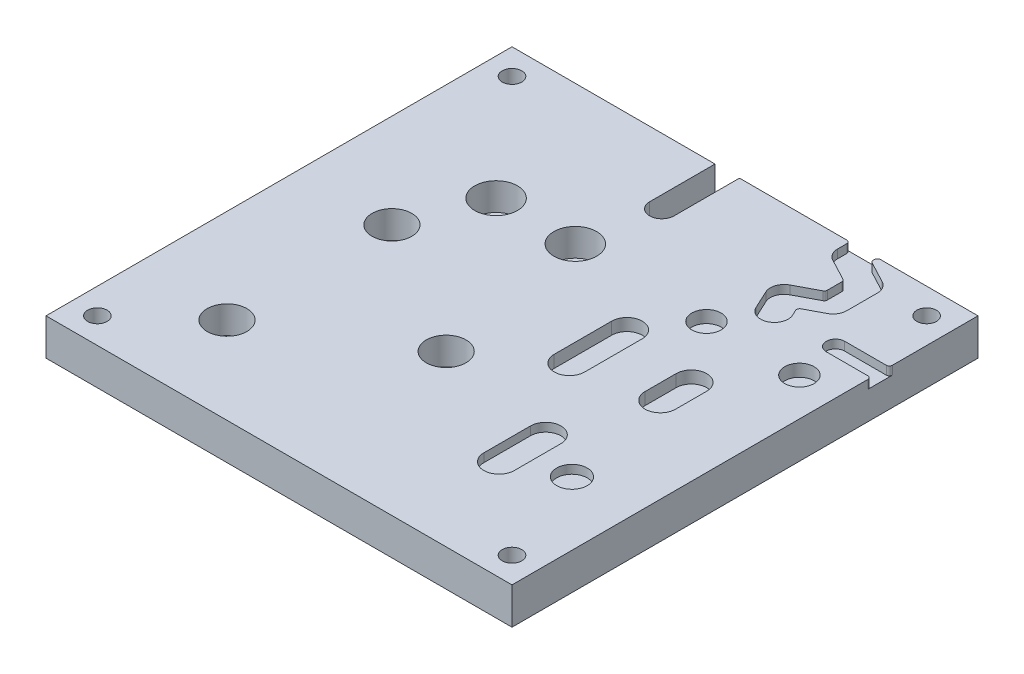
SolidWorks part; units mm, degrees
ref_plane "Front Plane" through (0, 0, 0) normal (0, 0, 1) x (1, 0, 0)
ref_plane "Top Plane" through (0, 0, 0) normal (0, 1, 0) x (1, 0, 0)
ref_plane "Right Plane" through (0, 0, 0) normal (1, 0, 0) x (0, 0, -1)
sketch "Base plate" plane through (0, 0, 0) normal (0, 1, 0) x (1, 0, 0)
  line L0 (-2.9, 38.1) -> (-2.9, 27.4) construction
  line L1 (-33.9, -38.1) -> (33.9, -38.1)
  line L2 (-38.1, -33.9) -> (-38.1, 33.9)
  line L3 (-33.9, 38.1) -> (33.9, 38.1)
  line L4 (38.1, -33.9) -> (38.1, 33.9)
  line L5 (-38.1, -38.1) -> (38.1, 38.1) construction
  line L6 (-38.1, 38.1) -> (38.1, -38.1) construction
  line L7 (-0.9, 38.1) -> (-0.9, 27.4)
  line L8 (-4.9, 38.1) -> (-4.9, 27.4)
  line L9 (-33.9, 38.1) -> (-38.1, 38.1)
  line L10 (-38.1, 38.1) -> (-38.1, 33.9)
  line L11 (-38.1, -33.9) -> (-38.1, -38.1)
  line L12 (-38.1, -38.1) -> (-33.9, -38.1)
  line L13 (33.9, -38.1) -> (38.1, -38.1)
  line L14 (38.1, -38.1) -> (38.1, -33.9)
  line L15 (38.1, 33.9) -> (38.1, 38.1)
  line L16 (38.1, 38.1) -> (33.9, 38.1)
  circle A0 centre (-33.9, 33.9) radius 1.6
  circle A1 centre (33.9, 33.9) radius 1.6
  circle A2 centre (33.9, -33.9) radius 1.6
  circle A3 centre (-33.9, -33.9) radius 1.6
  arc A4 (-33.9, -38.1) -> (-38.1, -33.9) centre (-33.9, -33.9) cw construction
  arc A5 (33.9, -38.1) -> (38.1, -33.9) centre (33.9, -33.9) ccw construction
  arc A6 (33.9, 38.1) -> (38.1, 33.9) centre (33.9, 33.9) cw construction
  arc A7 (-38.1, 33.9) -> (-33.9, 38.1) centre (-33.9, 33.9) cw construction
  arc A9 (-4.9, 27.4) -> (-0.9, 27.4) centre (-2.9, 27.4) ccw
  point P0 (0, 0)
  dimension "D2" = 3.2
  dimension "D4" = 4.2
  dimension "D5" = 2
  dimension "D6" = 12.7
  dimension "D1" = 76.2
  dimension "D3" = 4.2
  dimension "D7" = 39
extrude "凸台-拉伸1" add sketch "Base plate" along normal blind 6 contours A9 L8 L3 A7 L2 A4 L1 A5 L4 A6 L7 A3 A2 A1 A0 region at (0.0249, 0, 0.274)
fillet "圆角1" [suppressed] radius 1
sketch "草图1" plane through (0, 0, 0) normal (0, -1, 0) x (1, 0, 0)
  line L0 (456, 1824) -> (2280, 1824) construction
  line L1 (-33.9, -33.9) -> (33.9, -33.9) construction
  line L3 (-0.35, 10.415) -> (-22.7, 10.415) construction
  line L6 (11.4, 2) -> (11.4, -7.4) construction
  line L7 (13.9, 2) -> (13.9, -7.4)
  line L8 (8.9, 2) -> (8.9, -7.4)
  line L9 (24.1, -0.16) -> (24.1, -5.24) construction
  line L10 (26.6, -0.16) -> (26.6, -5.24)
  line L11 (21.6, -0.16) -> (21.6, -5.24)
  line L12 (24.1, -2.7) -> (11.4, -2.7) construction
  line L13 (19.6, 21.71) -> (19.6, 14.09) construction
  line L14 (22.1, 21.71) -> (22.1, 14.09)
  line L15 (17.1, 21.71) -> (17.1, 14.09)
  line L16 (30.8, -22.1) -> (38.1, -22.1) construction
  line L17 (30.8, -20.6) -> (38.1, -20.6)
  line L18 (30.8, -23.6) -> (38.1, -23.6)
  line L19 (27.7, 17.9) -> (19.6, 17.9) construction
  line L24 (16.7, -15.1) -> (31.9, -15.1) construction
  line L25 (38.1, -20.6) -> (38.1, -23.6)
  line L26 (24.4, -28.1) -> (24.4, -33.1) construction
  line L27 (26.65, -28.1) -> (26.65, -33.1)
  line L28 (22.15, -28.1) -> (22.15, -33.1)
  line L29 (20.8, -22.1) -> (19.4, -25.1) construction
  line L30 (22.8389, -23.0515) -> (21.4389, -26.0515)
  line L31 (18.7611, -21.1485) -> (17.3611, -24.1485)
  line L32 (19.4, -36.1) -> (19.4, -38.1) construction
  line L33 (-0.9, -38.1) -> (38.1, -38.1) construction
  line L34 (21.65, -36.1) -> (21.65, -38.1)
  line L35 (17.15, -36.1) -> (17.15, -38.1)
  line L36 (17.15, -38.1) -> (21.65, -38.1)
  line L37 (24.4, -30.6) -> (19.4, -30.6) construction
  line L38 (19.4, -25.1) -> (19.4, -36.1) construction
  line L39 (30.8, -22.1) -> (20.8, -22.1) construction
  line L40 (18.348, -34.1111) -> (22.15, -32.1)
  line L41 (25.452, -35.0889) -> (21.65, -37.1)
  line L42 (18.348, -27.0889) -> (22.15, -29.1)
  line L43 (25.452, -26.1111) -> (22.2111, -24.3968)
  line L44 (-22.7, 23.9) -> (-22.7, -3.07) construction
  line L46 (-33.9, -38.1) -> (33.9, -38.1) construction
  line L48 (38.1, 33.9) -> (38.1, -33.9) construction
  line L49 (-33.9, 38.1) -> (33.9, 38.1) construction
  line L50 (-38.1, 33.9) -> (-38.1, -33.9) construction
  circle A0 centre (-22.7, 23.9) radius 3.25
  circle A1 centre (-0.35, 10.415) radius 3.25
  circle A2 centre (-22.7, -3.07) radius 3.25
  circle A3 centre (-17.96, -15.36) radius 3.5
  circle A4 centre (-5.01, -15.36) radius 3.5
  arc A8 (13.9, 2) -> (8.9, 2) centre (11.4, 2) ccw
  arc A9 (8.9, -7.4) -> (13.9, -7.4) centre (11.4, -7.4) ccw
  arc A10 (26.6, -0.16) -> (21.6, -0.16) centre (24.1, -0.16) ccw
  arc A11 (21.6, -5.24) -> (26.6, -5.24) centre (24.1, -5.24) ccw
  circle A12 centre (27.7, 17.9) radius 2.5
  arc A13 (22.1, 21.71) -> (17.1, 21.71) centre (19.6, 21.71) ccw
  arc A14 (17.1, 14.09) -> (22.1, 14.09) centre (19.6, 14.09) ccw
  arc A15 (30.8, -20.6) -> (30.8, -23.6) centre (30.8, -22.1) ccw
  circle A21 centre (16.7, -15.1) radius 2.4
  circle A22 centre (31.9, -15.1) radius 2.4
  arc A25 (26.65, -28.1) -> (22.15, -28.1) centre (24.4, -28.1) ccw
  arc A26 (22.15, -33.1) -> (26.65, -33.1) centre (24.4, -33.1) ccw
  arc A27 (22.8389, -23.0515) -> (18.7611, -21.1485) centre (20.8, -22.1) ccw
  arc A28 (17.3611, -24.1485) -> (21.4389, -26.0515) centre (19.4, -25.1) ccw
  arc A29 (21.65, -36.1) -> (17.15, -36.1) centre (19.4, -36.1) ccw
  point P21 (11.4, -2.7)
  point P26 (24.1, -2.7)
  point P39 (19.6, 17.9)
  point P61 (24.4, -30.6)
  point P70 (20.1, -23.6)
  line M4 (-0.9, -38.1) -> (38.1, -38.1)
  line M6 (38.1, -38.1) -> (38.1, 38.1)
  dimension "D1" = 6.5
  dimension "D7" = 7
  dimension "D10" = 2.5
  dimension "D11" = 5
  dimension "D12" = 2.5
  dimension "D13" = 4.8
  dimension "D20" = 6.2
  dimension "D21" = 11.8
  dimension "D24" = 5.08
  dimension "D31" = 2.25
  dimension "D33" = 9.5
  dimension "D36" = 8.8
  dimension "D2" = 26.97
  dimension "D4" = 22.35
  dimension "D5" = 14.2
  dimension "D6" = 12.95
  dimension "D8" = 4.74
  dimension "D9" = 12.29
  dimension "D14" = 15.2
  dimension "D15" = 8.1
  dimension "D16" = 7.62
  dimension "D17" = 9.4
  dimension "D18" = 12.7
  dimension "D19" = 3
  dimension "D22" = 18.8
  dimension "D23" = 14
  dimension "D25" = 31.2
  dimension "D26" = 16
  dimension "D27" = 14.3
  dimension "D28" = 5
  dimension "D29" = 4.5
  dimension "D30" = 5
  dimension "D32" = 11
  dimension "D34" = 5
  dimension "D35" = 10
  dimension "D37" = 15.4
extrude "切除-拉伸1" cut sketch "草图1" along normal blind 4.5 from surface contours A1 | A0 | A2 | A3 | A4 region at (-22.7, 0, 23.9) region at (-0.35, 0, 10.415) starting at face at (-1.45, 6, -16.125)
extrude "切除-拉伸2" cut sketch "草图1<6>" along normal blind 2 from surface contours L8 A9 L7 A8 | L11 A11 L10 A10 | A22 | A21 region at (11.4, 0, -2.7) region at (24.1, 0, -2.7) starting at face at (-5.01, 6, -11.86)
sketch "草图1<6>" plane through (0, 0, 0) normal (0, -1, 0) x (1, 0, 0) same geometry as "草图1"
extrude "切除-拉伸3" cut sketch "草图1<7>" along normal blind 1.4 from surface contours L34 A29 L35 M4 | A29 L34 L41 A26 L28 L40 | A26 L27 A25 L28 | A28 L42 L28 A25 L43 L30 | L31 A28 L30 A27 | L17 A15 L18 M6 | L15 A14 L14 A13 | A12 region at (19.6, 0, 17.9) region at (19.4, 0, -36.183) region at (33.8543, 0, -22.1) region at (21.9, 0, -34.6) region at (24.4, 0, -30.6) region at (21.9038, 0, -26.6982) region at (20.1, 0, -23.6) region at (27.7, 0, 17.9) starting at face at (31.9, 6, -12.7)
sketch "草图1<7>" plane through (0, 0, 0) normal (0, -1, 0) x (1, 0, 0) same geometry as "草图1"
fillet "圆角2" radius 0.5 8 edges at (21.65, 5.3, -38.1) (17.15, 5.3, -38.1) (38.1, 5.3, -23.6) (38.1, 5.3, -20.6) (21.65, 5.3, -37.1) (22.15, 5.3, -32.1) (22.15, 5.3, -29.1) (22.2111, 5.3, -24.3968)
chamfer "倒角1" [suppressed] distance 0.4 angle 45
sketch "草图2" plane through (0, 0, 0) normal (0, 1, 0) x (1, 0, 0)
  line L0 (-38.1, 0) -> (38.1, 0) construction
  line L1 (-38.1, 38.1) -> (-38.1, -38.1) construction
  line L2 (38.1, -38.1) -> (38.1, 20.1) construction
  point P3 (-38.1, 0)
  point P6 (38.1, 0)
